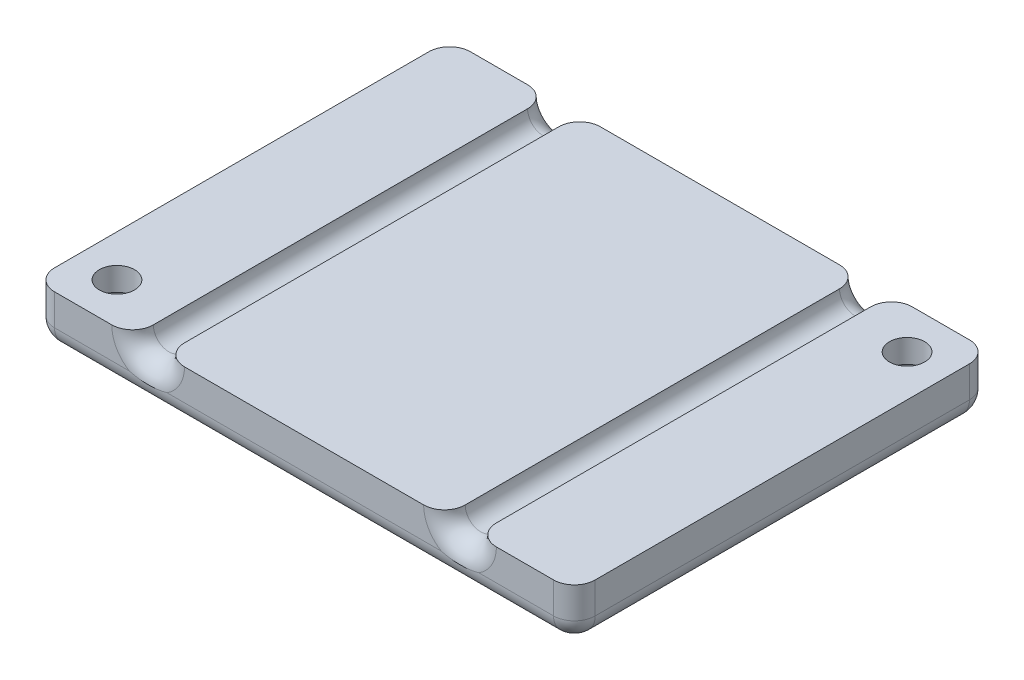
SolidWorks part; units mm, degrees
ref_plane "Front Plane" through (0, 0, 0) normal (0, 0, 1) x (1, 0, 0)
ref_plane "Top Plane" through (0, 0, 0) normal (0, 1, 0) x (1, 0, 0)
ref_plane "Right Plane" through (0, 0, 0) normal (1, 0, 0) x (0, 0, -1)
sketch "Sketch2" plane through (0, 0, 0) normal (0, 0, 1) x (1, 0, 0)
  line L1 (0, 0) -> (66.04, 0)
  line L2 (0, 0) -> (0, 6.35)
  line L3 (0, 6.35) -> (66.04, 6.35)
  line L4 (66.04, 0) -> (66.04, 6.35)
  dimension "D1" = 66.04
  dimension "D2" = 6.35
extrude "Boss-Extrude1" add sketch "Sketch2" along normal blind 50.8
sketch "Sketch3" plane through (0, 0, 50.8) normal (0, 0, 1) x (1, 0, 0)
  line L1 (66.04, 6.35) -> (0, 6.35) construction
  line L2 (13.97, 6.35) -> (52.07, 6.35) construction
  circle A0 centre (13.97, 6.35) radius 1.905
  circle A1 centre (52.07, 6.35) radius 1.905
  point P2 (44.0393, 6.35)
  point P7 (33.02, 6.35)
  point P8 (33.02, 6.35)
  dimension "D1" = 3.81
  dimension "D2" = 38.1
extrude "Cut-Extrude1" cut sketch "Sketch3" against normal through all
hole_wizard "CBORE for #6 Socket Head Cap Screw1" positions "Sketch4" profile "Sketch5" counterbore size "#6" standard "ANSI Inch" end condition through all
sketch "Sketch4" plane through (0, 0, 0) normal (0, -1, 0) x (-1, 0, 0)
  line L6 (0, 0) -> (-66.04, 0) construction
  line L7 (0, -50.8) -> (-66.04, -50.8) construction
  line L8 (-5.08, -45.72) -> (-60.96, -5.08) construction
  line L10 (-33.02, 0) -> (-33.02, -25.4) construction
  point P0 (-60.96, -5.08)
  point P2 (-5.08, -45.72)
  dimension "D1" = 5.08
  dimension "D2" = 55.88
  dimension "D3" = 5.08
sketch "Sketch5" plane through (60.96, 0, 5.08) normal (1, 0, 0) x (0, 0, -1)
  line L0 (0, 0) -> (0, 6.35)
  line L1 (0, 6.35) -> (2.1526, 6.35)
  line L3 (2.1526, 6.35) -> (2.1527, 3.5052)
  line L4 (2.1527, 3.5052) -> (3.5725, 3.5052)
  line L5 (3.5725, 3.5052) -> (3.5725, 0)
  line L7 (3.5725, 0) -> (0, 0)
  line L11 (0, -6.35) -> (0, 107.95) construction
  dimension "Thru Hole Dia." = 4.3053
  dimension "Thru Hole Depth" = 6.35
  dimension "C'Bore Dia." = 7.145
  dimension "C'Bore Depth" = 3.5052
fillet "Fillet1" radius 2.54 12 edges at (33.02, 0, 50.8) (0, 0, 25.4) (66.04, 0, 25.4) (33.02, 0, 0) (13.97, 4.445, 50.8) (13.97, 4.445, 0) (0, 3.175, 50.8) (66.04, 3.175, 50.8) (0, 3.175, 0) (66.04, 3.175, 0) (52.07, 4.445, 0) (52.07, 4.445, 50.8)
